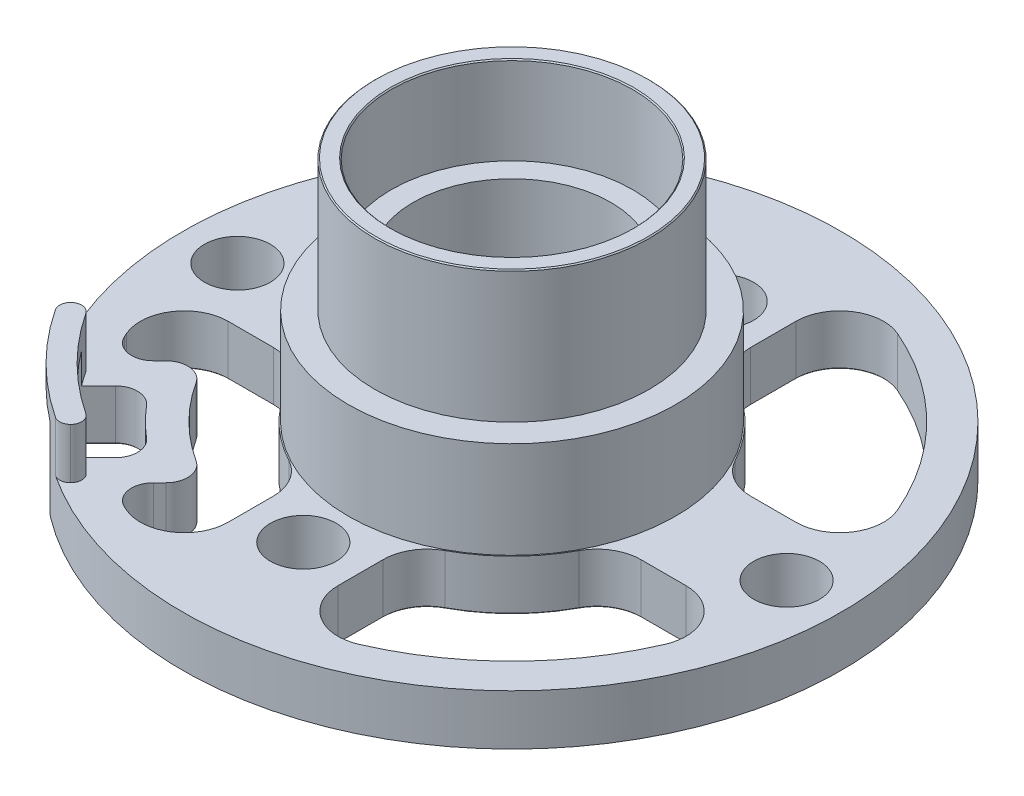
SolidWorks part; units mm, degrees
ref_plane "Спереди" through (0, 0, 0) normal (0, 0, 1) x (1, 0, 0)
ref_plane "Сверху" through (0, 0, 0) normal (0, 1, 0) x (1, 0, 0)
ref_plane "Справа" through (0, 0, 0) normal (1, 0, 0) x (0, 0, -1)
sketch "Эскиз1" plane through (0, 0, 0) normal (0, 1, 0) x (1, 0, 0)
  circle A0 centre (0, 0) radius 15
  dimension "D1" = 30
extrude "Бобышка-Вытянуть1" add sketch "Эскиз1" along normal blind 2.3
sketch "Эскиз2" plane through (0, 0, 0) normal (0, -1, 0) x (1, 0, 0)
  line L1 (14, 0) -> (11, 0) construction
  line L2 (2.5, 8.3666) -> (2.5, 10.4198)
  line L3 (2.5, -16.2534) -> (0, -16.2534)
  line L4 (2.5, -10.4198) -> (2.5, -8.3666)
  line L6 (-2.5, -10.4198) -> (-2.5, -8.3666)
  line L7 (1.4891, -9.6809) -> (1.3659, -8.88) construction
  line L8 (1.4891, 9.6809) -> (1.3659, 8.88) construction
  line L9 (-10.4198, -2.5) -> (-8.3666, -2.5)
  line L11 (-10.4198, 2.5) -> (-8.3666, 2.5)
  line L13 (-12.6273, -1.4946) -> (-12.0273, -1.4236) construction
  line L14 (-12.6273, 1.4946) -> (-12.0273, 1.4236) construction
  line L15 (0, -16.2534) -> (0, -19.7359) construction
  line L17 (-1.3659, 8.88) -> (-1.4891, 9.6809) construction
  line L18 (-2.5, 8.3666) -> (-2.5, 10.4198)
  line L25 (-1.3659, -8.88) -> (-1.4891, -9.6809) construction
  line L26 (0, -8) -> (0, -11) construction
  line L29 (8.3666, -2.5) -> (10.4198, -2.5)
  line L30 (12.0273, -1.4236) -> (12.6273, -1.4946) construction
  line L32 (12.0273, 1.4236) -> (12.6273, 1.4946) construction
  line L33 (8.3666, 2.5) -> (10.4198, 2.5)
  circle A0 centre (0, 9.5) radius 1.5
  circle A1 centre (0, -9.5) radius 1.5
  circle A2 centre (12.5, 0) radius 1.5
  circle A3 centre (-12.5, 0) radius 1.5
  arc A4 (12.2559, 5.293) -> (5.293, 12.2559) centre (0, 0) ccw
  arc A5 (-6.6052, -3.5526) -> (-3.5526, -6.6052) centre (0, 0) ccw
  arc A6 (6.6052, 3.5526) -> (3.5526, 6.6052) centre (0, 0) ccw
  arc A7 (-3.5526, 6.6052) -> (-6.6052, 3.5526) centre (0, 0) ccw
  arc A8 (3.5526, -6.6052) -> (6.6052, -3.5526) centre (0, 0) ccw
  arc A9 (-5.293, 12.2559) -> (-12.2559, 5.293) centre (0, 0) ccw
  arc A10 (5.293, -12.2559) -> (12.2559, -5.293) centre (0, 0) ccw
  arc A11 (-12.2559, -5.293) -> (-5.293, -12.2559) centre (0, 0) ccw
  arc A12 (-10.4198, -2.5) -> (-12.2559, -5.293) centre (-10.4198, -4.5) ccw
  arc A13 (-8.3666, -2.5) -> (-6.6052, -3.5526) centre (-8.3666, -4.5) cw
  arc A14 (-2.5, -8.3666) -> (-3.5526, -6.6052) centre (-4.5, -8.3666) ccw
  arc A15 (-2.5, -10.4198) -> (-5.293, -12.2559) centre (-4.5, -10.4198) cw
  arc A16 (2.5, -10.4198) -> (5.293, -12.2559) centre (4.5, -10.4198) ccw
  arc A17 (2.5, -8.3666) -> (3.5526, -6.6052) centre (4.5, -8.3666) cw
  arc A18 (8.3666, -2.5) -> (6.6052, -3.5526) centre (8.3666, -4.5) ccw
  arc A19 (10.4198, -2.5) -> (12.2559, -5.293) centre (10.4198, -4.5) cw
  arc A20 (10.4198, 2.5) -> (12.2559, 5.293) centre (10.4198, 4.5) ccw
  arc A21 (8.3666, 2.5) -> (6.6052, 3.5526) centre (8.3666, 4.5) cw
  arc A22 (2.5, 8.3666) -> (3.5526, 6.6052) centre (4.5, 8.3666) ccw
  arc A23 (2.5, 10.4198) -> (5.293, 12.2559) centre (4.5, 10.4198) cw
  arc A24 (-2.5, 10.4198) -> (-5.293, 12.2559) centre (-4.5, 10.4198) ccw
  arc A25 (-2.5, 8.3666) -> (-3.5526, 6.6052) centre (-4.5, 8.3666) cw
  arc A26 (-8.3666, 2.5) -> (-6.6052, 3.5526) centre (-8.3666, 4.5) ccw
  arc A27 (-10.4198, 2.5) -> (-12.2559, 5.293) centre (-10.4198, 4.5) cw
  point P29 (-13.1138, -2.5)
  point P55 (-2.5, -13.1138)
  point P61 (2.5, -13.1138)
  point P64 (2.5, -7.0711)
  point P73 (7.0711, 2.5)
  point P76 (2.5, 7.0711)
  point P81 (-2.5, 13.1138)
  point P84 (-2.5, 7.0711)
  point P89 (-13.1138, 2.5)
  dimension "D1" = 3
  dimension "D2" = 3
  dimension "D3" = 3
  dimension "D4" = 3
  dimension "D9" = 26.7
  dimension "D10" = 15
  dimension "D11" = 2
  dimension "D5" = 25
  dimension "D6" = 12.5
  dimension "D7" = 19
  dimension "D8" = 9.5
extrude "Вырез-Вытянуть1" cut sketch "Эскиз2" against normal blind 2.3 contours A27 L11 A26 A7 A25 L18 A24 A9 | A0 | A23 L2 A22 A6 A21 L33 A20 A4 | A2 | A19 L29 A18 A8 A17 L4 A16 A10 | A1 | A15 L6 A14 A5 A13 L9 A12 A11 | A3 region at (7.2608, 0, 7.2608) region at (7.2608, 0, -7.2608) region at (-7.2608, 0, -7.2608) region at (-7.2608, 0, 7.2608) region at (0, 0, 9.5) region at (0, 0, -9.5) region at (12.5, 0, 0) region at (-12.5, 0, 0)
sketch "Эскиз3" plane through (0, 0, 0) normal (0, -1, 0) x (1, 0, 0)
  line L0 (-5.4762, 10.2845) -> (-7.9264, 12.7347)
  line L4 (0, 0) -> (-17.5213, 17.5213) construction
  line L6 (0, 0) -> (-21.467, 0) construction
  line L7 (-10.2845, 5.4762) -> (-12.7347, 7.9264)
  arc A0 (-12.7347, 7.9264) -> (-7.9264, 12.7347) centre (0, 0) cw
  circle A1 centre (0, 0) radius 15 construction
  arc A2 (-8.7373, 5.6409) -> (-5.6409, 8.7373) centre (0, 0) cw
  arc A3 (-8.7373, 5.6409) -> (-10.2845, 5.4762) centre (-9.5774, 6.1833) cw
  arc A4 (-5.6409, 8.7373) -> (-5.4762, 10.2845) centre (-6.1833, 9.5774) ccw
  dimension "D2" = 4.6
  dimension "D1" = 1
  dimension "D3" = 3.4
  dimension "D4" = 3.4
extrude "Бобышка-Вытянуть2" add sketch "Эскиз3" against normal blind 4.6
sketch "Эскиз4" plane through (0, 0, 0) normal (0, -1, 0) x (1, 0, 0)
  line L3 (-8.3439, 8.3439) -> (-14.3626, 14.3626) construction
  line L13 (-7.6091, 10.4375) -> (-11.3621, 14.1906)
  line L15 (-11.3621, 14.1906) -> (-14.1906, 11.3621)
  line L16 (-10.4375, 7.6091) -> (-14.1906, 11.3621)
  line L18 (-11.3621, 14.1906) -> (-7.3752, 9.2112) construction
  line L19 (-5.4762, 10.2845) -> (-6.7244, 11.5328) construction
  line L21 (-9.2112, 7.3752) -> (-14.1906, 11.3621) construction
  arc A22 (-8.9702, 7.6665) -> (-7.6665, 8.9702) centre (0, 0) cw
  arc A23 (-5.6409, 8.7373) -> (-8.7373, 5.6409) centre (0, 0) ccw construction
  arc A24 (-8.9702, 7.6665) -> (-10.4375, 7.6091) centre (-9.7304, 8.3162) cw
  arc A25 (-7.6665, 8.9702) -> (-7.6091, 10.4375) centre (-8.3162, 9.7304) ccw
  dimension "D1" = 1.4
  dimension "D3" = 1
  dimension "D2" = 1.4
extrude "Вырез-Вытянуть2" cut sketch "Эскиз4" against normal blind 3.7
sketch "Эскиз5" plane through (0, 4.6, 0) normal (0, 1, 0) x (1, 0, 0)
  line L0 (-12.9379, -5.3489) -> (-9.1095, -3.7661)
  line L1 (-9.1095, -3.7661) -> (-3.9795, -8.0387)
  line L2 (-3.9795, -8.0387) -> (-5.1383, -13.023)
  arc A0 (-5.1383, -13.023) -> (-12.9379, -5.3489) centre (0, 0) cw
  arc A1 (-12.7347, -7.9264) -> (-7.9264, -12.7347) centre (0, 0) ccw construction
  dimension "D1" = 1
extrude "Вырез-Вытянуть3" cut sketch "Эскиз5" against normal up to surface (2.3 mm away) up to face at (-5.8001, 2.3, 5.8001)
fillet "Скругление1" radius 1 2 edges at (-6.7244, 1.15, 11.5328) (-11.5328, 1.15, 6.7244)
sketch "Эскиз6" plane through (0, 2.3, 0) normal (0, 1, 0) x (1, 0, 0)
  circle A0 centre (0, 0) radius 7.45
  dimension "D1" = 14.9
extrude "Бобышка-Вытянуть3" add sketch "Эскиз6" along normal blind 4.4
sketch "Эскиз7" plane through (0, 6.7, 0) normal (0, 1, 0) x (1, 0, 0)
  circle A0 centre (0, 0) radius 6.25
  dimension "D1" = 12.5
extrude "Бобышка-Вытянуть4" add sketch "Эскиз7" along normal blind 6
sketch "Эскиз8" plane through (0, 12.7, 0) normal (0, 1, 0) x (1, 0, 0)
  circle A0 centre (0, 0) radius 5.5
  dimension "D1" = 11
extrude "Вырез-Вытянуть4" cut sketch "Эскиз8" against normal blind 4
sketch "Эскиз9" plane through (0, 0, 0) normal (0, -1, 0) x (1, 0, 0)
  circle A0 centre (0, 0) radius 4.5
  dimension "D1" = 9
extrude "Вырез-Вытянуть5" cut sketch "Эскиз9" against normal through all
sketch "Эскиз10" plane through (0, 0, 0) normal (0, -1, 0) x (1, 0, 0)
  circle A0 centre (0, 0) radius 5.5
  dimension "D1" = 11
extrude "Вырез-Вытянуть6" cut sketch "Эскиз10" against normal blind 4
chamfer "Фаска1" distance 0.05 angle 45 48 edges at (-8.3534, 0, 11.1818) (-7.317, 0, 9.6913) (-8.3439, 0, 8.3439) (-9.6913, 0, 7.317) (-11.1818, 0, 8.3534) (0, 12.7, 6.25) (0, 12.7, 5.5) (0, 0, -5.5) (2.5, 0, 9.3932) (2.7832, 0, 7.3406) (3.4013, 0, 12.091) (5.3033, 0, 5.3033) (9.4399, 0, 9.4399) (7.3406, 0, 2.7832) (12.091, 0, 3.4013) (9.3932, 0, 2.5) (-5.6159, 0, 10.4242) (-5.1889, 0, 9.4716) (-6.0319, 0, 11.4521) (-7.3539, 0, 7.3539) (-5.3752, 0, 12.22) (-9.4716, 0, 5.1889) (-3.4013, 0, 12.091) (-10.4242, 0, 5.6159) (-2.5, 0, 9.3932) (-11.4521, 0, 6.0319) (-2.7832, 0, 7.3406) (-12.22, 0, 5.3752) (-5.3033, 0, 5.3033) (-12.091, 0, 3.4013) (-7.3406, 0, 2.7832) (-9.3932, 0, 2.5) (-7.3406, 0, -2.7832) (-5.3033, 0, -5.3033) (-9.3932, 0, -2.5) (-2.7832, 0, -7.3406) (-12.091, 0, -3.4013) (-2.5, 0, -9.3932) (-9.4399, 0, -9.4399) (-3.4013, 0, -12.091) (5.3033, 0, -5.3033) (2.7832, 0, -7.3406) (7.3406, 0, -2.7832) (2.5, 0, -9.3932) (9.3932, 0, -2.5) (3.4013, 0, -12.091) (12.091, 0, -3.4013) (9.4399, 0, -9.4399)
fillet "Скругление2" radius 0.5 4 edges at (-7.9264, 3.45, 12.7347) (-7.199, 3.45, 12.0073) (-12.7347, 3.45, 7.9264) (-12.0073, 3.45, 7.199)
